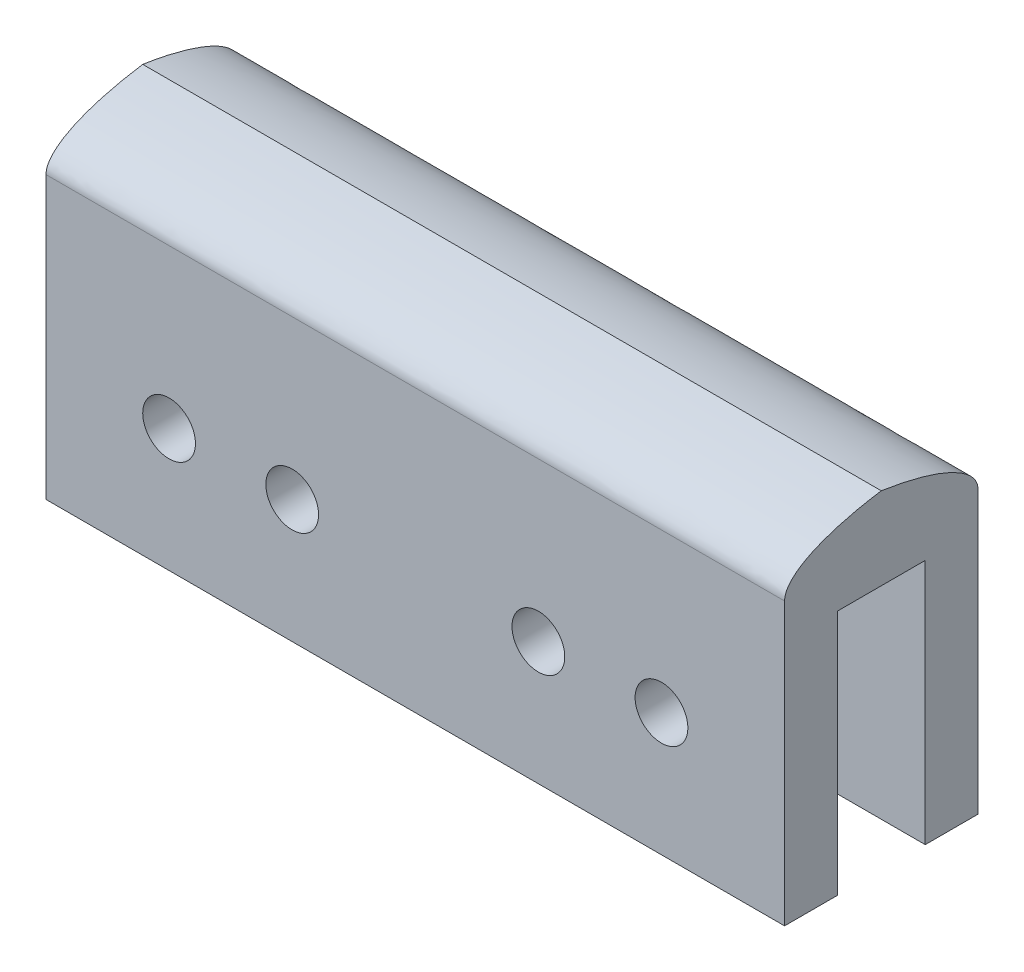
SolidWorks part; units mm, degrees
ref_plane "Front Plane" through (0, 0, 0) normal (0, 0, 1) x (1, 0, 0)
ref_plane "Top Plane" through (0, 0, 0) normal (0, 1, 0) x (1, 0, 0)
ref_plane "Right Plane" through (0, 0, 0) normal (1, 0, 0) x (0, 0, -1)
sketch "Sketch1" plane through (0, 0, 0) normal (0, 1, 0) x (1, 0, 0)
  line L0 (0, 0) -> (0, -3)
  line L1 (0, 0) -> (42, 0)
  line L2 (0, 0) -> (0, -11)
  line L3 (0, -11) -> (42, -11)
  line L4 (42, 0) -> (42, -11)
  line L5 (0, -11) -> (0, -8)
  line L6 (0, -3) -> (42, -3)
  line L7 (0, -8) -> (42, -8)
extrude "Boss-Extrude1" add sketch "Sketch1" along normal blind 14 contours L0 L6 L4 L1 | L7 L2 L3 L4 region at (21, 0, 1.5) region at (21, 0, 9.5)
sketch "Sketch2" plane through (0, 0, 0) normal (0, 0, -1) x (-1, 0, 0)
  line L0 (-42, 7) -> (0, 7)
  line L1 (-42, 14) -> (-42, 0) construction
  line L2 (0, 14) -> (0, 0) construction
  line L3 (-42, 7) -> (-35, 7)
  line L4 (-35, 7) -> (-28, 7)
  line L5 (-28, 7) -> (-14, 7)
  line L6 (-14, 7) -> (-7, 7)
  circle A0 centre (-35, 7) radius 1.5
  circle A1 centre (-28, 7) radius 1.5
  circle A2 centre (-14, 7) radius 1.5
  circle A3 centre (-7, 7) radius 1.5
extrude "Cut-Extrude1" cut sketch "Sketch2" against normal blind 14 contours L0 A0 L3 | L3 A0 L0 | L0 A1 | L0 A1 | L0 A3 | L0 A3 | A2 region at (35, 7.6366, 0) region at (35, 6.3634, 0) region at (7, 7.6366, 0) region at (7, 6.3634, 0) region at (28, 7.6366, 0) region at (28, 6.3634, 0)
sketch "Sketch3" plane through (0, 14, 0) normal (0, 1, 0) x (1, 0, 0)
  line L1 (0, -11) -> (42, -11)
  line L2 (0, -11) -> (0, 0)
  line L3 (0, 0) -> (42, 0)
  line L4 (42, -11) -> (42, 0)
extrude "Boss-Extrude2" add sketch "Sketch3" along normal blind 5
fillet "Fillet1" radius 3 2 edges at (21, 19, 0) (21, 19, 11) second distance 10 first distance on face at (33.5, 7, 0) first distance on face at (21, 9.5, 11)
